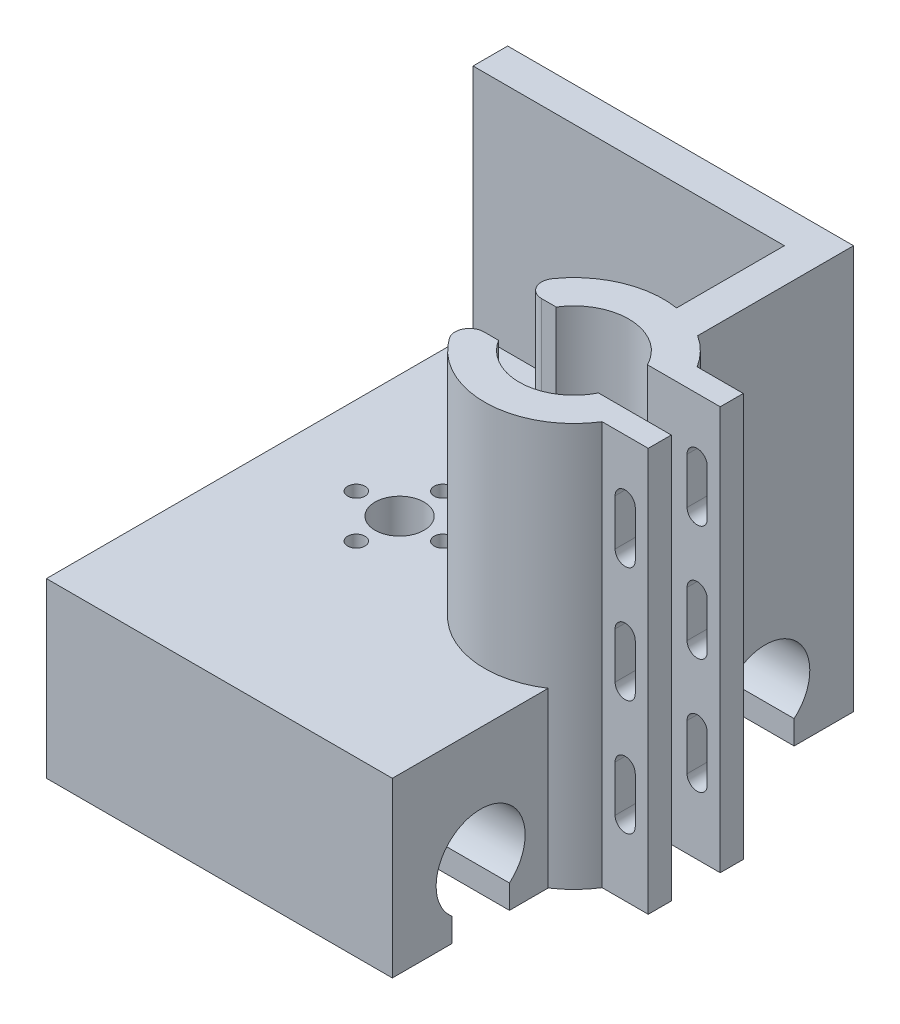
SolidWorks part; units mm, degrees
ref_plane "Front Plane" through (0, 0, 0) normal (0, 0, 1) x (1, 0, 0)
ref_plane "Top Plane" through (0, 0, 0) normal (0, 1, 0) x (1, 0, 0)
ref_plane "Right Plane" through (0, 0, 0) normal (1, 0, 0) x (0, 0, -1)
sketch "Sketch1" plane through (0, 0, 0) normal (1, 0, 0) x (0, 0, -1)
  line L0 (-24.69, 0) -> (24.69, 0) construction
  line L1 (-40, 20) -> (40, 20)
  line L2 (-40, 20) -> (-40, -10)
  line L3 (-40, -10) -> (-29.69, -10)
  line L4 (40, 20) -> (40, -10)
  line L5 (24.69, 0) -> (0, 0) construction
  line L6 (-29.69, -5.882) -> (-29.69, -10)
  line L7 (-19.69, -5.882) -> (-19.69, -10)
  line L8 (19.69, -5.882) -> (19.69, -10)
  line L9 (29.69, -5.882) -> (29.69, -10)
  line L10 (-19.69, -10) -> (19.69, -10)
  line L11 (29.69, -10) -> (40, -10)
  arc A0 (-19.69, -5.882) -> (-29.69, -5.882) centre (-24.69, 0) ccw
  arc A1 (29.69, -5.882) -> (19.69, -5.882) centre (24.69, 0) ccw
  point P5 (0, 20)
  dimension "D3" = 15.44
  dimension "D4" = 15.44
  dimension "D5" = 10
  dimension "D1" = 49.38
  dimension "D2" = 80
  dimension "D6" = 10
  dimension "D7" = 10
  dimension "D8" = 20
extrude "Main Base" add sketch "Sketch1" along normal blind 60
sketch "Holes_Sketch" plane through (0, 20, 0) normal (0, 1, 0) x (1, 0, 0)
  line L0 (30, -40) -> (30, 40) construction
  line L1 (60, -40) -> (0, -40)
  line L2 (60, -40) -> (60, 40)
  line L3 (60, 40) -> (0, 40)
  line L4 (0, -40) -> (0, 40)
  line L5 (60, 0) -> (0, 0) construction
  line L6 (17, 40) -> (17, -40) construction
  line L7 (61, 40) -> (61, -40) construction
  line L8 (10.5, 40) -> (10.5, -40) construction
  line L9 (25.5, 40) -> (25.5, -40) construction
  line L10 (32, -40) -> (32, 40) construction
  circle A0 centre (21.25, 0) radius 4.25 construction
  circle A1 centre (51.5, 0) radius 9.5
  circle A2 centre (13.75, 0) radius 1.5
  circle A3 centre (13.75, 0) radius 3.25 construction
  circle A4 centre (21.25, -7.5) radius 1.5
  circle A5 centre (21.25, 0) radius 4.25 construction
  circle A6 centre (28.75, 0) radius 1.5
  circle A7 centre (21.25, 0) radius 4.25
  circle A8 centre (21.25, 7.5) radius 1.5
  circle A9 centre (21.25, 0) radius 4.25
  circle A10 centre (28.75, 0) radius 3.25
  point P8 (30, 0)
  point P11 (30, 0)
  point P39 (21.25, 0)
  dimension "D1" = 8.5
  dimension "D2" = 19
  dimension "D4" = 3
  dimension "D5" = 6.5
  dimension "D6" = 21.5
  dimension "D9" = 6.5
  dimension "D3" = 44
  dimension "D8" = 1
  dimension "D7" = 4
extrude "Holes" cut sketch "Holes_Sketch" against normal up to surface (30 mm away) contours A7 | A4 | A2 | A6 | A8 | A1 | A8 region at (51.3167, 20, 0) region at (13.75, 20, 0) region at (21.25, 20, 7.5) region at (28.75, 20, 0) region at (21.25, 20, 0) region at (21.25, 20, -7.5) up to face at (30, -10, 0)
sketch "Sketch3" plane through (0, 20, 0) normal (0, 1, 0) x (1, 0, 0)
  line L0 (0, 34) -> (60, 34)
  line L1 (0, 40) -> (60, 40)
  line L2 (0, 40) -> (0, -40)
  line L3 (0, -40) -> (60, -40)
  line L4 (60, 40) -> (60, 7.5)
  line L5 (60, 4.2426) -> (72.6266, 4.2426)
  line L6 (60, -4.2426) -> (72.6266, -4.2426)
  line L7 (0, 0) -> (60, 0) construction
  line L8 (30, 40) -> (30, -40) construction
  line L9 (43.4223, 5) -> (40.8816, 5)
  line L10 (43.4223, -5) -> (40.8816, -5)
  line L11 (60, -4.2426) -> (59.9089, -4.2732)
  line L12 (72.6266, 4.2426) -> (72.6266, 8.2426)
  line L13 (54, 15.2971) -> (54, 34)
  line L14 (72.6266, 8.2426) -> (64.6266, 8.2426)
  line L15 (60, -7.5) -> (60, -40)
  line L16 (60, 7.5) -> (60, -7.5) construction
  line L17 (64.6266, 8.2426) -> (64.6266, 4.2426) construction
  line L18 (72.6266, -4.2426) -> (72.6266, -8.2426)
  line L19 (72.6266, -8.2426) -> (64.6266, -8.2426)
  line L20 (64.6266, -8.2426) -> (64.6266, -4.2426) construction
  circle A0 centre (51.5, 0) radius 9.5 construction
  arc A1 (43.4223, -5) -> (60, -4.2426) centre (51.5, 0) ccw
  arc A2 (64.6266, 8.2426) -> (38.8396, 8.9423) centre (51.5, 0) ccw
  circle A3 centre (51.5, 0) radius 15.5 construction
  arc A4 (38.8396, -8.9423) -> (64.6266, -8.2426) centre (51.5, 0) ccw
  circle A5 centre (51.5, 0) radius 9.5 construction
  arc A6 (40.8816, 5) -> (38.8396, 8.9423) centre (40.8816, 7.5) cw
  arc A7 (40.8816, -5) -> (38.8396, -8.9423) centre (40.8816, -7.5) ccw
  arc A8 (60, 4.2426) -> (43.4223, 5) centre (51.5, 0) ccw
  point P20 (30, 0)
  point P21 (30, 0)
  point P30 (36.8286, -5)
  arc M1 (60, -4.2426) -> (60, 4.2426) centre (51.5, 0) cw
  line M7 (0, 40) -> (0, -40)
  line M9 (60, -40) -> (60, -4.2426)
  line M10 (60, 40) -> (0, 40)
  line M44 (60, 4.2426) -> (60, 40)
  dimension "D2" = 6
  dimension "D5" = 2.5
  dimension "D6" = 4
  dimension "D1" = 6
  dimension "D3" = 5
  dimension "D4" = 5
  dimension "D7" = 6
  dimension "D8" = 8
  dimension "D9" = 8
  dimension "D10" = 4
extrude "Boss-Extrude3" add sketch "Sketch3" along normal blind 40 contours L10 A7 A4 L15 M9 M1 | A6 L9 A2 M1 M44 | A2 L4 L0 L13 | L0 M7 M44 M10 region at (30, 20, -37) region at (57.0589, 20, -24.1742) region at (49.5659, 20, -10.6781) region at (49.5659, 20, 10.6781)
extrude "Boss-Extrude4" add sketch "Sketch3<6>" along normal up to surface and the other way up to surface contours L15 A4 M9 | A2 M44 region at (65.3892, 20, 6.9731) region at (65.3892, 20, -6.9731) up to face at (48.271, 60, 8.934) other way up to face at (21.25, -10, -6)
sketch "Sketch3<6>" plane through (0, 20, 0) normal (0, 1, 0) x (1, 0, 0) same geometry as "Sketch3"
sketch "Sketch4" plane through (0, -10, 0) normal (0, -1, 0) x (1, 0, 0)
  line L0 (31.65, 1.6743) -> (28.75, 3.3486)
  line L1 (22.9243, 4.6) -> (24.5986, 7.5)
  line L2 (24.5986, 7.5) -> (22.9243, 10.4)
  line L3 (22.9243, 10.4) -> (19.5757, 10.4)
  line L4 (19.5757, 10.4) -> (17.9014, 7.5)
  line L5 (17.9014, 7.5) -> (19.5757, 4.6)
  line L6 (19.5757, 4.6) -> (22.9243, 4.6)
  line L7 (28.75, 3.3486) -> (25.85, 1.6743)
  line L8 (25.85, 1.6743) -> (25.85, -1.6743)
  line L9 (25.85, -1.6743) -> (28.75, -3.3486)
  line L10 (28.75, -3.3486) -> (31.65, -1.6743)
  line L11 (31.65, -1.6743) -> (31.65, 1.6743)
  line L12 (22.9243, -10.4) -> (24.5986, -7.5)
  line L13 (24.5986, -7.5) -> (22.9243, -4.6)
  line L14 (22.9243, -4.6) -> (19.5757, -4.6)
  line L15 (19.5757, -4.6) -> (17.9014, -7.5)
  line L16 (17.9014, -7.5) -> (19.5757, -10.4)
  line L17 (19.5757, -10.4) -> (22.9243, -10.4)
  line L18 (10.85, -1.6743) -> (13.75, -3.3486)
  line L19 (13.75, -3.3486) -> (16.65, -1.6743)
  line L20 (16.65, -1.6743) -> (16.65, 1.6743)
  line L21 (16.65, 1.6743) -> (13.75, 3.3486)
  line L22 (13.75, 3.3486) -> (10.85, 1.6743)
  line L23 (10.85, 1.6743) -> (10.85, -1.6743)
  circle A0 centre (21.25, 0) radius 4.25 construction
  circle A1 centre (21.25, 7.5) radius 1.5 construction
  circle A2 centre (13.75, 0) radius 1.5 construction
  circle A3 centre (21.25, -7.5) radius 1.5 construction
  circle A4 centre (28.75, 0) radius 1.5 construction
  circle A5 centre (21.25, 0) radius 4.25
  circle A6 centre (21.25, 7.5) radius 1.5
  circle A7 centre (13.75, 0) radius 1.5
  circle A8 centre (21.25, -7.5) radius 1.5
  circle A9 centre (28.75, 0) radius 1.5
  circle A10 centre (21.25, 7.5) radius 2.9 construction
  point P43 (21.25, 0)
  dimension "D1" = 5.8
  dimension "D2" = 4
extrude "Cut-Extrude2" cut sketch "Sketch4" against normal blind 20
sketch "Sketch7" plane through (0, 0, -8.2426) normal (0, 0, -1) x (-1, 0, 0)
  line L0 (-68.6266, 50) -> (-68.6266, 42) construction
  line L1 (-66.8766, 50) -> (-66.8766, 42)
  line L2 (-70.3766, 50) -> (-70.3766, 42)
  line L3 (-64.6266, 25) -> (-72.6266, 25) construction
  line L4 (-64.6266, 60) -> (-64.6266, -10) construction
  line L5 (-72.6266, 60) -> (-72.6266, -10) construction
  line L6 (-68.6266, 60) -> (-68.6266, -10) construction
  line L7 (-72.6266, 60) -> (-64.6266, 60) construction
  line L8 (-64.6266, -10) -> (-72.6266, -10) construction
  line L9 (-68.6266, 30) -> (-68.6266, 22) construction
  line L10 (-66.8766, 30) -> (-66.8766, 22)
  line L11 (-70.3766, 30) -> (-70.3766, 22)
  line L12 (-68.6266, 10) -> (-68.6266, 2) construction
  line L13 (-66.8766, 10) -> (-66.8766, 2)
  line L14 (-70.3766, 10) -> (-70.3766, 2)
  arc A0 (-66.8766, 50) -> (-70.3766, 50) centre (-68.6266, 50) ccw
  arc A1 (-70.3766, 42) -> (-66.8766, 42) centre (-68.6266, 42) ccw
  arc A2 (-66.8766, 30) -> (-70.3766, 30) centre (-68.6266, 30) ccw
  arc A3 (-70.3766, 22) -> (-66.8766, 22) centre (-68.6266, 22) ccw
  arc A4 (-66.8766, 10) -> (-70.3766, 10) centre (-68.6266, 10) ccw
  arc A5 (-70.3766, 2) -> (-66.8766, 2) centre (-68.6266, 2) ccw
  point P2 (-68.6266, 46)
  point P13 (-68.6266, 25)
  point P20 (-68.6266, 25)
  point P24 (-68.6266, 26)
  point P31 (-68.6266, 6)
  dimension "D1" = 8
  dimension "D2" = 3.5
  dimension "D4" = 10
  dimension "D3" = 3
extrude "Cut-Extrude3" cut sketch "Sketch7" against normal up to surface (16.4853 mm away) up to face at (68.6266, 25, 8.2426)
